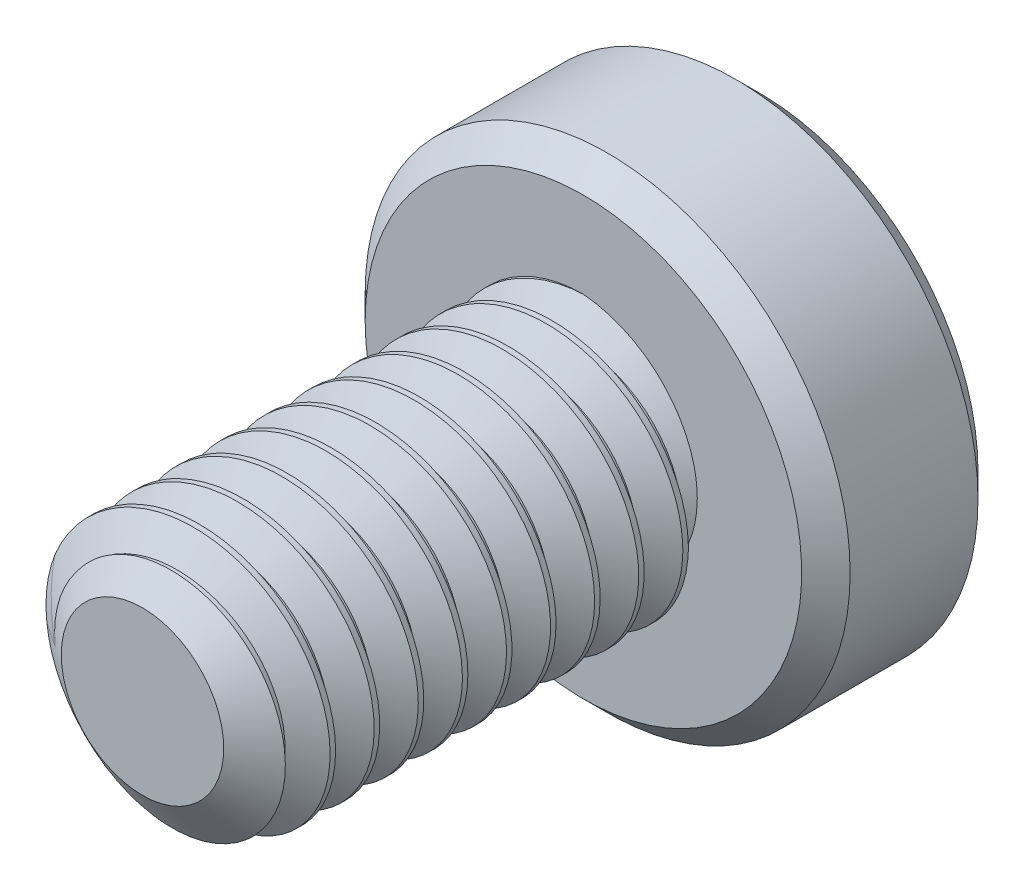
SolidWorks part; units mm, degrees
other "DetailItem1"
ref_plane "Front Plane" through (0, 0, 0) normal (0, 0, 1) x (1, 0, 0)
ref_plane "Top Plane" through (0, 0, 0) normal (0, 1, 0) x (1, 0, 0)
ref_plane "Right Plane" through (0, 0, 0) normal (1, 0, 0) x (0, 0, -1)
sketch "Sketch1" plane through (0, 0, 0) normal (0, 0, 1) x (1, 0, 0)
  circle A0 centre (0, 0) radius 1.5
  dimension "OD" = 3
extrude "Extrude1" add sketch "Sketch1" against normal blind 5
sketch "Sketch2" plane through (0, 0, 0) normal (0, 0, 1) x (1, 0, 0)
  circle A0 centre (0, 0) radius 1.5 construction
  circle A1 centre (0, 0) radius 1.5
curve "Helix/Spiral1" pitch 0.5 height 5.5 radius 1.5 centre (0, 0, 0) axis (0, 0, -1) start towards (0, 1, 0) parameters "pitch"=0.5
sketch "Sketch3" plane through (0, 0, 0) normal (1, 0, 0) x (0, 0, -1)
  line L0 (-0.4375, 1.5) -> (-0.25, 1.1752)
  line L1 (-0.25, 1.1752) -> (-0.1875, 1.1752)
  line L2 (-0.1875, 1.1752) -> (0, 1.5)
  line L3 (-0.4375, 1.5) -> (0, 1.5)
  line L4 (-0.2187, 1.5) -> (-0.2187, 1.1752) construction
  line L5 (-0.3438, 1.3376) -> (-0.0938, 1.3376) construction
  line L6 (0, 1.5) -> (0, -1.5) construction
  dimension "D1" = 0.0625
  dimension "D2" = 0.25
  dimension "D3" = 60
sweep "Cut-Sweep1" cut profiles "Sketch3" path "Helix/Spiral1" align with end faces yes
sketch "Sketch4" plane through (0, 0, 0) normal (1, 0, 0) x (0, 0, -1)
  line L0 (0.4053, 1.5) -> (0, 0.9212)
  line L1 (0, 0.9212) -> (0, 1.5)
  line L2 (0.4053, 1.5) -> (0, 1.5)
  line L3 (-0.4375, 1.5) -> (0, 1.5) construction
  line L4 (0, 0) -> (7.0209, 0) construction
  dimension "D1" = 55
  dimension "D2" = 0.254
revolve "Cut-Revolve1" cut sketch "Sketch4" angle 360 about L4
sketch "Sketch6" plane through (0, 0, -5) normal (0, 0, -1) x (-1, 0, 0)
  circle A0 centre (0, 0) radius 2.75
  dimension "head dia" = 5.5
extrude "Extrude2" add sketch "Sketch6" along normal blind 2
sketch "Sketch7" plane through (0, 0, -7) normal (0, 0, -1) x (-1, 0, 0)
  line L1 (0, 1.1547) -> (-1, 0.5774)
  line L2 (-1, 0.5774) -> (-1, -0.5774)
  line L3 (-1, -0.5774) -> (0, -1.1547)
  line L4 (0, -1.1547) -> (1, -0.5774)
  line L5 (1, -0.5774) -> (1, 0.5774)
  line L6 (1, 0.5774) -> (0, 1.1547)
  circle A0 centre (0, 0) radius 1 construction
  dimension "hex dia" = 2
extrude "Cut-Extrude1" cut sketch "Sketch7" against normal blind 1.5
sketch "Sketch8" plane through (0, 0, -7) normal (0, 0, -1) x (-1, 0, 0)
  circle A0 centre (0, 0) radius 1.1547
extrude "Cut-Extrude2" cut sketch "Sketch8" against normal through all draft 45
chamfer "Chamfer1" distance 0.275 angle 45 2 edges at (-2.75, 0, -7) (-2.75, 0, -5)
sketch "Sketch10" plane through (0, 0, -5) normal (0, 0, 1) x (1, 0, 0)
  circle A1 centre (0, 0) radius 1.5
  circle A2 centre (0, 0) radius 1.5
  dimension "D1" = 0
ref_plane "Plane1" through (0, 0, -38.1) normal (0, 0, 1) x (1, 0, 0)
extrude "partial thread" [suppressed] add sketch "Sketch10" along normal up to surface (8 mm away) separate body up to plane "Plane1"
chamfer "Chamfer2" [suppressed] distance 0.06 angle 45
combine bodies "Combine1" [suppressed] operation type add bodies to combine 107 108
sketch "Sketch9" plane through (0, 0, 0) normal (1, 0, 0) x (0, 0, -1)
  line L0 (0, 1.5) -> (0, -1.5) construction
  line L1 (1.25, 1.5) -> (1.25, -1.5) construction
  dimension "D1" = 1.25
equation "\"D3@Helix/Spiral1\" = \"screw length@Extrude1\"+\"pitch@Helix/Spiral1\""
equation "\"D1@Sketch3\" = \"pitch@Helix/Spiral1\"*.125"
equation "\"D2@Sketch3\" = \"pitch@Helix/Spiral1\"*.5"
equation "\"D1@Cut-Extrude1\" = \"hex dia@Sketch7\"*.75"
equation "\"D1@Chamfer1\" = \"head dia@Sketch6\"*.05"
equation "\"D1@Sketch9\" = \"pitch@Helix/Spiral1\"*2.5"
equation "\"D1@Chamfer2\"=\"OD@Sketch1\"*.02"
